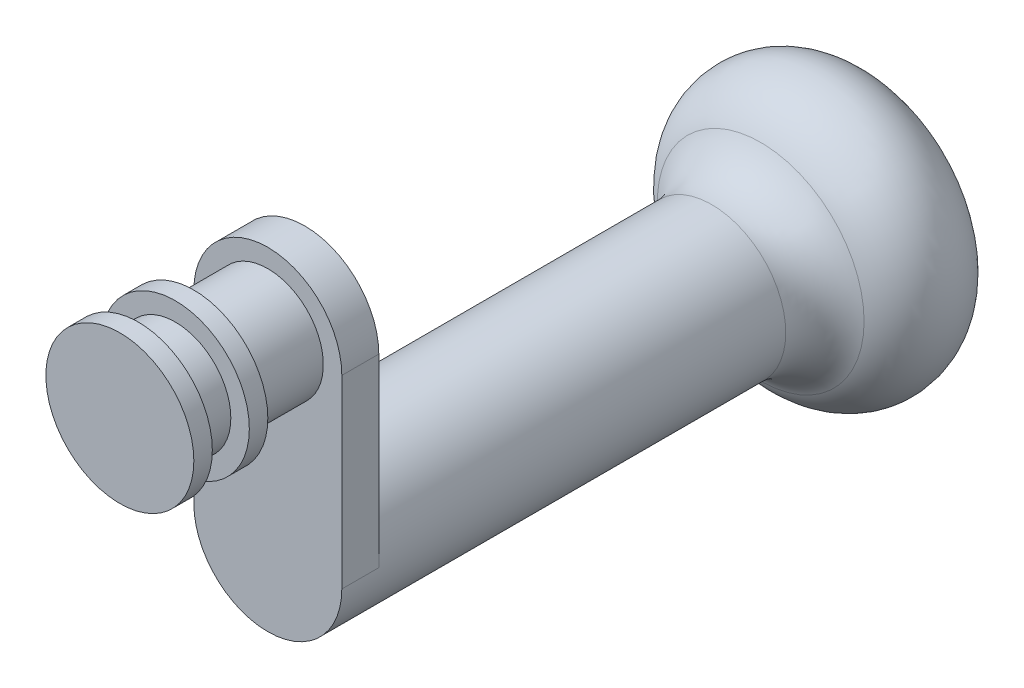
SolidWorks part; units mm, degrees
material "Plain Carbon Steel"
ref_plane "Front Plane" through (0, 0, 0) normal (0, 0, 1) x (1, 0, 0)
ref_plane "Top Plane" through (0, 0, 0) normal (0, 1, 0) x (1, 0, 0)
ref_plane "Right Plane" through (0, 0, 0) normal (1, 0, 0) x (0, 0, -1)
sketch "Sketch1" plane through (0, 0, 0) normal (0, 0, 1) x (1, 0, 0)
  circle A0 centre (0, 0) radius 7.5
  dimension "D1" = 15
extrude "Boss-Extrude1" add sketch "Sketch1" along normal blind 25
sketch "Sketch2" plane through (0, 0, 25) normal (0, 0, 1) x (1, 0, 0)
  circle A0 centre (0, 0) radius 10
  dimension "D1" = 20
extrude "Boss-Extrude2" add sketch "Sketch2" against normal blind 2.5
extrude "Boss-Extrude3" add sketch "Sketch2<2>" against normal blind 2.5 from offset 7.5 offset against normal yes
sketch "Sketch2<2>" plane through (0, 0, 25) normal (0, 0, 1) x (1, 0, 0) same geometry as "Sketch2"
sketch "Sketch4" plane through (0, 0, 0) normal (0, 0, -1) x (-1, 0, 0)
  line L0 (-10, 0) -> (-10, -25)
  line L1 (10, 0) -> (10, -25)
  circle A0 centre (0, 0) radius 10 construction
  arc A1 (10, 0) -> (-10, 0) centre (0, 0) ccw
  arc A3 (-10, -25) -> (10, -25) centre (0, -25) ccw
  dimension "D1" = 25
extrude "Boss-Extrude4" add sketch "Sketch4" against normal blind 5
sketch "Sketch5" plane through (0, 0, 5) normal (0, 0, 1) x (1, 0, 0)
  circle A0 centre (0, -25) radius 10
  arc A2 (-10, -25) -> (10, -25) centre (0, -25) ccw construction
extrude "Boss-Extrude5" add sketch "Sketch5" against normal blind 57.5
sketch "Sketch6" plane through (0, 0, 0) normal (1, 0, 0) x (0, 0, -1)
  line L0 (52.5, -25) -> (77.5, -25)
  line L1 (52.5, -35) -> (52.5, -15) construction
  line L2 (52.5, -15) -> (55, -15)
  line L3 (77.5, -15) -> (77.5, -25)
  line L4 (52.5, -15) -> (52.5, -25)
  arc A0 (55, -15) -> (61.6176, -11.0294) centre (55, -7.5) ccw
  arc A1 (61.6176, -11.0294) -> (77.5, -15) centre (69.0625, -15) cw
  dimension "D3" = 7.5
  dimension "D1" = 25
  dimension "D2" = 2.5
  dimension "D4" = 10
revolve "Revolve1" add sketch "Sketch6" angle 360 about L0
